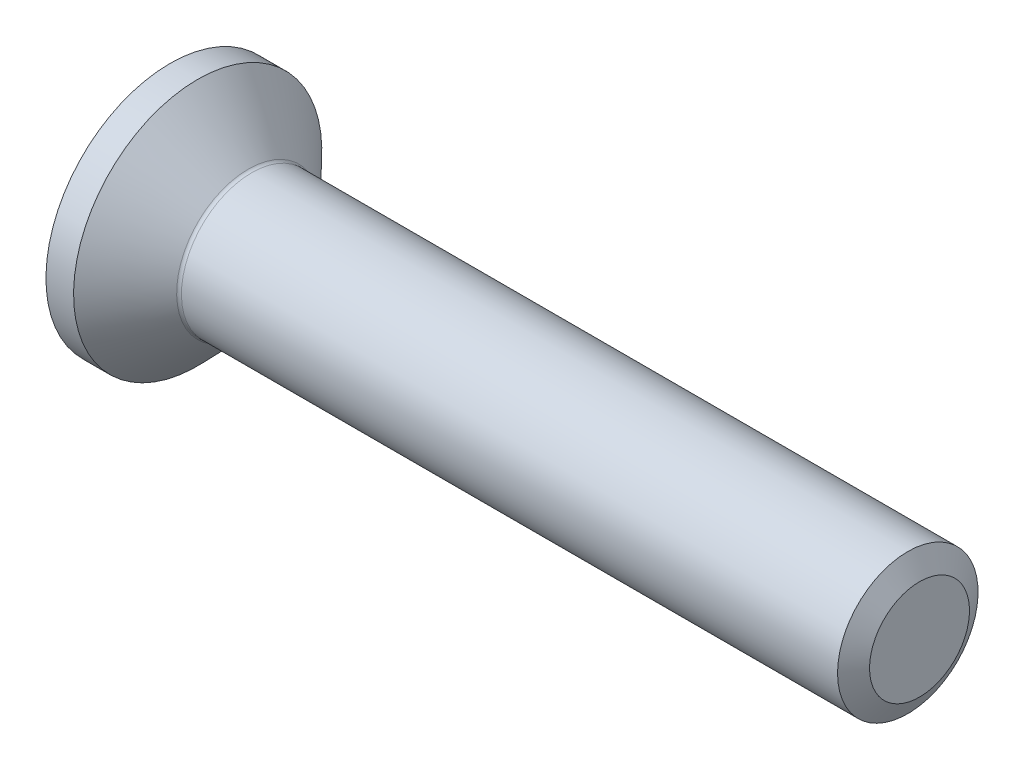
SolidWorks part; units mm, degrees
ref_plane "前视基准面" through (0, 0, 0) normal (0, 0, 1) x (1, 0, 0)
ref_plane "上视基准面" through (0, 0, 0) normal (0, 1, 0) x (1, 0, 0)
ref_plane "右视基准面" through (0, 0, 0) normal (1, 0, 0) x (0, 0, -1)
sketch "尺寸草图" plane through (0, 0, 0) normal (0, 0, 1) x (1, 0, 0)
  line L0 (0, 0) -> (16, 0) construction
  line L1 (16, 0) -> (16, 1.5) construction
  line L2 (16, 1.5) -> (15.5, 1.5) construction
  line L3 (15.5, 1.5) -> (4, 1.5) construction
  line L4 (0, 3.36) -> (1.86, 3.36) construction
  line L5 (1.86, 3.36) -> (1.96, 3.36) construction
  point P3 (16, 1.65)
  point P7 (0, 3.36)
  point P8 (0, 1.5)
  point P9 (0, 2.3)
  point P13 (0, 1)
  point P15 (1.1, 3.36)
  point P16 (1.71, 3.36)
  dimension "l" = 16
  dimension "d" = 3
  dimension "P" = 0.5
  dimension "b" = 12
  dimension "da" = 3.3
  dimension "dk" = 6.72
  dimension "ds" = 3
  dimension "e" = 2.3
  dimension "k" = 1.86
  dimension "r" = 0.1
  dimension "s" = 2
  dimension "t" = 1.1
  dimension "w" = 0.25
sketch "草图1" plane through (0, 0, 0) normal (0, 0, 1) x (1, 0, 0)
  line L0 (0, 1.5) -> (-14.2576, 1.5)
  line L1 (-14.3295, 1.5305) -> (-15.4105, 2.65)
  line L2 (-15.4105, 2.65) -> (-16, 2.65)
  line L3 (-16, 2.65) -> (-16, 0)
  line L4 (-16, 0) -> (0, 0)
  line L5 (0, 0) -> (0, 1.5)
  line L6 (0, 0) -> (-16, 0) construction
  arc A0 (-14.2576, 1.5) -> (-14.3295, 1.5305) centre (-14.2576, 1.6) cw
  point P9 (-14.3, 1.5)
  dimension "r" = 0.1
  dimension "k" = 1.7
  dimension "dk" = 5.3
  dimension "l" = 16
  dimension "D5" = 46
  dimension "d" = 3
revolve "旋转1" add sketch "草图1" angle 360 about L6
cosmetic thread "装饰螺纹线1" parameters "b"=12, "D2"=2.4
sketch "草图2" plane through (-16, 0, 0) normal (-1, 0, 0) x (0, 0, 1)
  line L0 (0, 0) -> (0, 1.5) construction
  line L1 (0, 1.1547) -> (-1, 0.5774)
  line L2 (-1, 0.5774) -> (-1, -0.5774)
  line L3 (-1, -0.5774) -> (0, -1.1547)
  line L4 (0, -1.1547) -> (1, -0.5774)
  line L5 (1, -0.5774) -> (1, 0.5774)
  line L6 (1, 0.5774) -> (0, 1.1547)
  circle A0 centre (0, 0) radius 1 construction
  point P1 (0, 1.1453)
  dimension "s" = 2
  dimension "e" = 2.3
extrude "切除-拉伸1" cut sketch "草图2" against normal blind 1.86
sketch "草图6" plane through (0, 0, 0) normal (0, 0, 1) x (1, 0, 0)
  line L0 (-14.9, 1.1547) -> (-14.2333, 0)
  line L1 (-14.2333, 0) -> (-13.84, 0)
  line L2 (-13.84, 0) -> (-13.84, 1.1547)
  line L3 (-13.84, 1.1547) -> (-14.9, 1.1547)
  line L4 (-16, 0) -> (-14.14, 0) construction
  line L5 (-16, 0) -> (-18.3, 0) construction
  dimension "D1" = 60
  dimension "t" = 1.1
  dimension "t1" = 1.86
  dimension "e-s" = 0.3
  dimension "e" = 2.3
revolve "旋转2" add sketch "草图6" angle 360 about L4
sketch "草图7" plane through (0, 0, 0) normal (0, 0, 1) x (1, 0, 0)
  line L0 (-16, 1.1547) -> (-16, 0)
  line L1 (-16, 0) -> (-15.7, 0)
  line L2 (-15.7, 0) -> (-16, 1.1547)
  line L3 (-16, 0) -> (-15.7, 0) construction
  dimension "e-s*1.1" = 0.3
revolve "切除-旋转2" cut sketch "草图7" angle 360 about L3
sketch "草图4" plane through (0, 0, 0) normal (0, 0, 1) x (1, 0, 0)
  line L0 (-0.25, 1.5) -> (0, 1.067)
  line L1 (0, -1.5) -> (0, 1.5) construction
  line L2 (0, 1.067) -> (0.25, 1.5)
  line L3 (0.25, 1.5) -> (-0.25, 1.5)
  line L4 (-0.25, 0) -> (0.25, 0) construction
  dimension "d" = 3
  dimension "p" = 0.5
revolve "切除-旋转1" cut sketch "草图4" angle 360 about L4
ref_axis "基准轴1" through (-21.1715, 0, 0) along (1, 0, 0)
pattern_linear "阵列(线性)2" [suppressed] count 24 spacing 0.5 along (-1, 0, 0) of bodies 104
